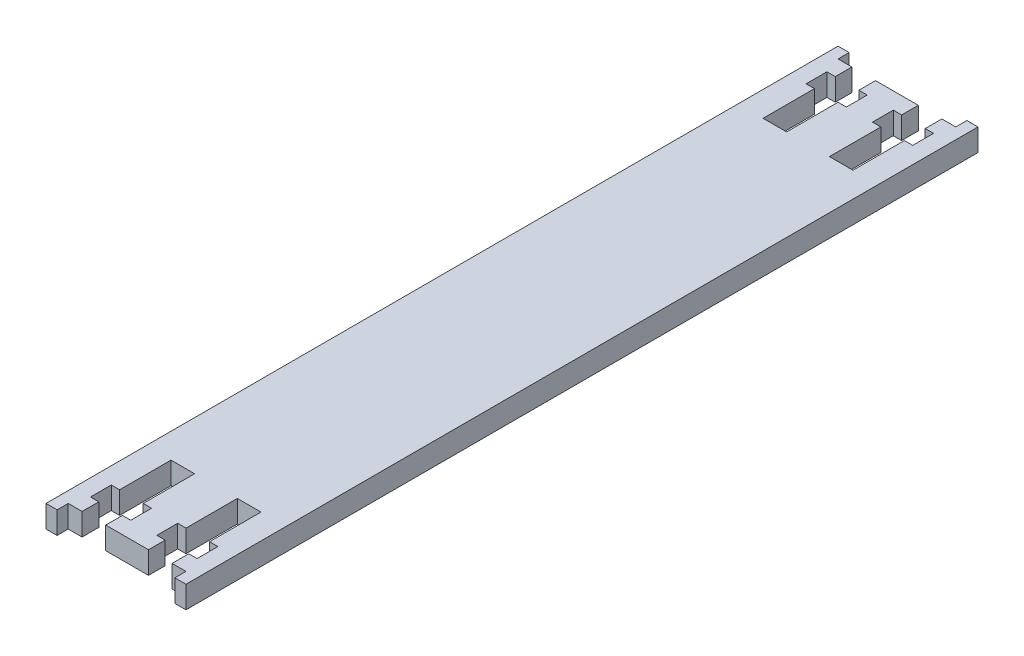
SolidWorks part; units mm, degrees
ref_plane "Front Plane" through (0, 0, 0) normal (0, 0, 1) x (1, 0, 0)
ref_plane "Top Plane" through (0, 0, 0) normal (0, 1, 0) x (1, 0, 0)
ref_plane "Right Plane" through (0, 0, 0) normal (1, 0, 0) x (0, 0, -1)
sketch "Sketch1" plane through (0, 0, 0) normal (0, 1, 0) x (1, 0, 0)
  line L0 (13.8906, 220) -> (13.8906, 215.2375)
  line L1 (3.175, 0) -> (7.1437, 0)
  line L2 (0, 0) -> (0, 220)
  line L3 (3.175, 220) -> (7.1437, 220)
  line L4 (40, 0) -> (40, 220)
  line L5 (20, 220) -> (20, 0) construction
  line L6 (0, 110) -> (40, 110) construction
  line L7 (13.8906, 215.2375) -> (16.2719, 215.2375)
  line L8 (16.2719, 215.2375) -> (16.2719, 209.2844)
  line L9 (16.2719, 209.2844) -> (13.8906, 209.2844)
  line L10 (13.8906, 209.2844) -> (13.8906, 194.6)
  line L11 (13.8906, 194.6) -> (7.1437, 194.6)
  line L12 (7.1437, 194.6) -> (7.1437, 209.2844)
  line L13 (7.1437, 209.2844) -> (4.7625, 209.2844)
  line L14 (4.7625, 209.2844) -> (4.7625, 215.2375)
  line L15 (4.7625, 215.2375) -> (7.1437, 215.2375)
  line L16 (7.1437, 215.2375) -> (7.1437, 220)
  line L17 (23.7281, 215.2375) -> (23.7281, 209.2844)
  line L18 (32.8562, 215.2375) -> (32.8562, 220)
  line L19 (35.2375, 215.2375) -> (32.8562, 215.2375)
  line L20 (35.2375, 209.2844) -> (35.2375, 215.2375)
  line L21 (32.8562, 209.2844) -> (35.2375, 209.2844)
  line L22 (32.8562, 194.6) -> (32.8562, 209.2844)
  line L23 (26.1094, 194.6) -> (32.8562, 194.6)
  line L24 (26.1094, 209.2844) -> (26.1094, 194.6)
  line L25 (23.7281, 209.2844) -> (26.1094, 209.2844)
  line L26 (26.1094, 215.2375) -> (23.7281, 215.2375)
  line L27 (26.1094, 220) -> (26.1094, 215.2375)
  line L28 (26.1094, 0) -> (26.1094, 4.7625)
  line L29 (26.1094, 4.7625) -> (23.7281, 4.7625)
  line L30 (23.7281, 10.7156) -> (26.1094, 10.7156)
  line L31 (26.1094, 10.7156) -> (26.1094, 25.4)
  line L32 (26.1094, 25.4) -> (32.8563, 25.4)
  line L33 (32.8563, 25.4) -> (32.8563, 10.7156)
  line L34 (32.8563, 10.7156) -> (35.2375, 10.7156)
  line L35 (35.2375, 10.7156) -> (35.2375, 4.7625)
  line L36 (35.2375, 4.7625) -> (32.8563, 4.7625)
  line L37 (32.8563, 4.7625) -> (32.8563, 0)
  line L38 (23.7281, 4.7625) -> (23.7281, 10.7156)
  line L39 (16.2719, 4.7625) -> (16.2719, 10.7156)
  line L40 (7.1437, 4.7625) -> (7.1437, 0)
  line L41 (4.7625, 4.7625) -> (7.1437, 4.7625)
  line L42 (4.7625, 10.7156) -> (4.7625, 4.7625)
  line L43 (7.1437, 10.7156) -> (4.7625, 10.7156)
  line L44 (7.1437, 25.4) -> (7.1437, 10.7156)
  line L45 (13.8906, 25.4) -> (7.1437, 25.4)
  line L46 (13.8906, 10.7156) -> (13.8906, 25.4)
  line L47 (16.2719, 10.7156) -> (13.8906, 10.7156)
  line L48 (13.8906, 4.7625) -> (16.2719, 4.7625)
  line L49 (13.8906, 0) -> (13.8906, 4.7625)
  line L50 (13.8906, 220) -> (26.1094, 220)
  line L51 (32.8562, 220) -> (36.825, 220)
  line L52 (13.8906, 0) -> (26.1094, 0)
  line L53 (32.8563, 0) -> (36.825, 0)
  line L54 (0, 220) -> (0, 223.175)
  line L55 (0, 223.175) -> (3.175, 223.175)
  line L56 (3.175, 223.175) -> (3.175, 220)
  line L57 (36.825, 223.175) -> (36.825, 220)
  line L58 (40, 223.175) -> (36.825, 223.175)
  line L59 (40, 220) -> (40, 223.175)
  line L60 (40, 0) -> (40, -3.175)
  line L61 (40, -3.175) -> (36.825, -3.175)
  line L62 (36.825, -3.175) -> (36.825, 0)
  line L63 (3.175, -3.175) -> (3.175, 0)
  line L64 (0, -3.175) -> (3.175, -3.175)
  line L65 (0, 0) -> (0, -3.175)
  point P57 (20, 110)
  point P160 (20, 110)
  dimension "D1" = 220
  dimension "D2" = 40
  dimension "D3" = 6.7469
  dimension "D4" = 5.9531
  dimension "D5" = 25.4
  dimension "D6" = 4.7625
  dimension "D7" = 11.5094
  dimension "D8" = 4.7625
  dimension "D9" = 3.175
extrude "Boss-Extrude1" add sketch "Sketch1" along normal blind 6.35
